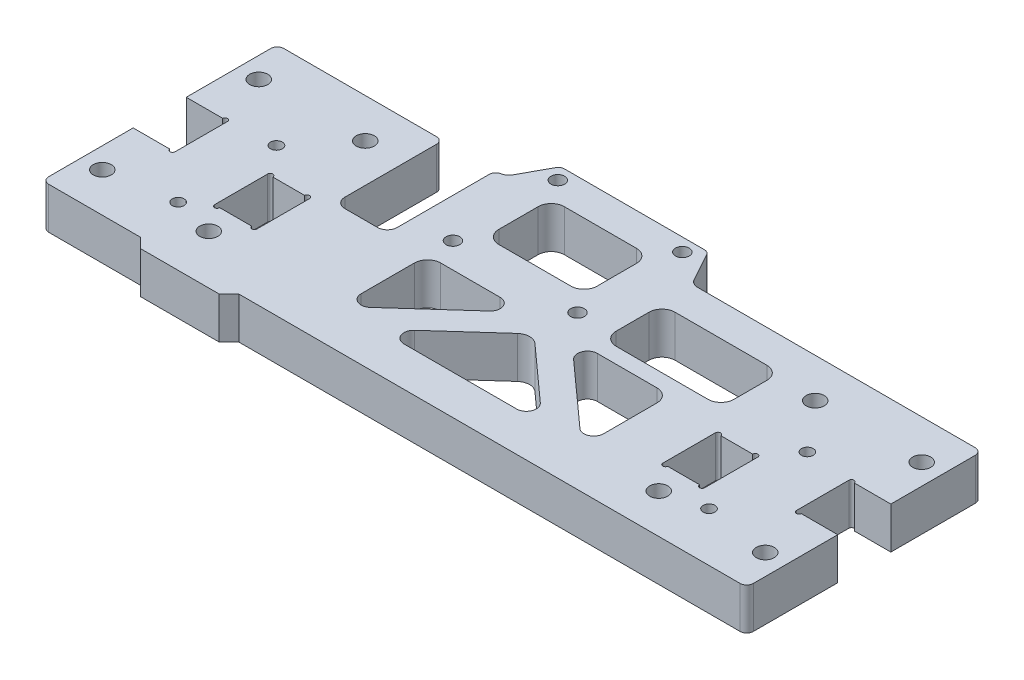
SolidWorks part; units mm, degrees
material "6061 Alloy"
ref_plane "Front Plane" through (0, 0, 0) normal (0, 0, 1) x (1, 0, 0)
ref_plane "Top Plane" through (0, 0, 0) normal (0, 1, 0) x (1, 0, 0)
ref_plane "Right Plane" through (0, 0, 0) normal (1, 0, 0) x (0, 0, -1)
sketch "Sketch1" plane through (0, 0, 0) normal (0, 1, 0) x (1, 0, 0)
  line L0 (107.5, 76.65) -> (107.5, 0) construction
  line L6 (32.7004, 36.1) -> (32.7004, 19.9)
  line L8 (45.6, 36) -> (45.6, 20)
  line L13 (0, 71.75) -> (69.5, 71.75)
  line L14 (69.5, 71.75) -> (75.5, 82.75)
  line L15 (75.5, 82.75) -> (120.5, 82.75)
  line L16 (120.5, 82.75) -> (126.5, 71.75)
  line L17 (126.5, 71.75) -> (215, 71.75)
  line L18 (32.7004, 28) -> (45.6, 28) construction
  line L19 (34.3004, 36.1) -> (44.0063, 36.1)
  line L20 (34.3004, 19.9) -> (44.0063, 19.9)
  line L21 (182.2996, 36.1) -> (182.2996, 19.9)
  line L22 (180.6996, 36.1) -> (170.9937, 36.1)
  line L23 (169.4, 36) -> (169.4, 20)
  line L24 (180.6996, 19.9) -> (170.9937, 19.9)
  line L25 (12.7, 35.875) -> (0, 35.875) construction
  line L29 (12.7, 43.975) -> (12.7, 27.775)
  line L30 (11.1189, 43.975) -> (0, 43.975)
  line L31 (11.1189, 27.775) -> (0, 27.775)
  line L32 (0, 27.775) -> (0, 0)
  line L33 (0, 43.975) -> (0, 71.75)
  line L34 (202.3, 35.875) -> (215, 35.875) construction
  line L35 (215, 43.975) -> (215, 71.75)
  line L36 (215, 27.775) -> (215, 0)
  line L37 (203.8811, 27.775) -> (215, 27.775)
  line L38 (203.8811, 43.975) -> (215, 43.975)
  line L39 (202.3, 43.975) -> (202.3, 27.775)
  line L40 (0, 0) -> (30, 0)
  line L41 (30, 0) -> (33, -3)
  line L42 (33, -3) -> (57, -3)
  line L43 (57, -3) -> (60, 0)
  line L44 (60, 0) -> (215, 0)
  circle A0 centre (38.85, 59.75) radius 2.75
  circle A5 centre (38.85, 12) radius 2.75
  circle A6 centre (176.15, 59.75) radius 2.75
  circle A7 centre (176.15, 12) radius 2.75
  arc A8 (32.7004, 36.1) -> (34.3004, 36.1) centre (33.5004, 36.1) cw
  arc A9 (45.6, 36) -> (44.0063, 36.1) centre (44.8, 36) ccw
  arc A10 (32.7004, 19.9) -> (34.3004, 19.9) centre (33.5004, 19.9) ccw
  arc A11 (45.6, 20) -> (44.0063, 19.9) centre (44.8, 20) cw
  arc A12 (182.2996, 19.9) -> (180.6996, 19.9) centre (181.4996, 19.9) cw
  arc A13 (182.2996, 36.1) -> (180.6996, 36.1) centre (181.4996, 36.1) ccw
  arc A14 (169.4, 36) -> (170.9937, 36.1) centre (170.2, 36) cw
  arc A15 (169.4, 20) -> (170.9937, 19.9) centre (170.2, 20) ccw
  circle A16 centre (6.35, 12) radius 2.75
  circle A17 centre (6.35, 59.75) radius 2.75
  arc A18 (12.7, 27.775) -> (11.1189, 27.775) centre (11.9095, 27.8976) cw
  arc A19 (12.7, 43.975) -> (11.1189, 43.975) centre (11.9095, 43.8524) ccw
  arc A20 (202.3, 43.975) -> (203.8811, 43.975) centre (203.0905, 43.8524) cw
  arc A21 (202.3, 27.775) -> (203.8811, 27.775) centre (203.0905, 27.8976) ccw
  circle A22 centre (208.65, 59.75) radius 2.75
  circle A23 centre (208.65, 12) radius 2.75
  dimension "D12" = 5.5
  dimension "D16" = 5.5
  dimension "D17" = 0.8
  dimension "D18" = 0.8
  dimension "D19" = 0.8
  dimension "D20" = 0.8
  dimension "D21" = 5.5
  dimension "D22" = 5.5
  dimension "D27" = 0.8
  dimension "D1" = 215
  dimension "D2" = 71.75
  dimension "D5" = 61.9
  dimension "D6" = 12.9
  dimension "D4" = 11
  dimension "D7" = 6
  dimension "D8" = 38
  dimension "D10" = 45
  dimension "D11" = 16.2
  dimension "D14" = 6
  dimension "D13" = 12
  dimension "D25" = 16.2
  dimension "D3" = 12
  dimension "D23" = 16.2
  dimension "D26" = 12.7
  dimension "D9" = 3
  dimension "D15" = 30
  dimension "D24" = 30
  dimension "D28" = 3
  dimension "D29" = 35.875
extrude "Boss-Extrude1" add sketch "Sketch1" along normal blind 12.7
sketch "Sketch2" plane through (0, 12.7, 0) normal (0, 1, 0) x (1, 0, 0)
  line L1 (50.6, 85.2461) -> (66.6, 85.2461)
  line L2 (50.6, 85.2461) -> (50.6, 38.75)
  line L3 (50.6, 38.75) -> (66.6, 38.75)
  line L4 (66.6, 85.2461) -> (66.6, 38.75)
  line L5 (45.6, 20) -> (45.6, 36) construction
  line L12 (69.5, 71.75) -> (0, 71.75) construction
  dimension "D1" = 5
  dimension "D2" = 16
  dimension "D3" = 33
extrude "Cut-Extrude1" cut sketch "Sketch2" against normal through all
sketch "Sketch3" plane through (0, 12.7, 0) normal (0, 1, 0) x (1, 0, 0)
  line L1 (66.6, 38.75) -> (66.6, 71.75) construction
  line L2 (120.5, 82.75) -> (75.5, 82.75) construction
  circle A0 centre (78.6, 78.75) radius 2.1
  circle A1 centre (78.6, 46.75) radius 2.1
  circle A2 centre (116.6, 78.75) radius 2.1
  circle A3 centre (116.6, 46.75) radius 2.1
  dimension "D2" = 4.2
  dimension "D5" = 4.2
  dimension "D8" = 32
  dimension "D1" = 4
  dimension "D3" = 12
  dimension "D4" = 32
  dimension "D7" = 38
  dimension "D6" = 2
extrude "Cut-Extrude2" cut sketch "Sketch3" against normal through all
sketch "Sketch5" plane through (0, 12.7, 0) normal (0, 1, 0) x (1, 0, 0)
  line L2 (83.6069, 16.5062) -> (102.789, 33.7701)
  line L3 (100.7821, 39) -> (82.6, 39)
  line L8 (78.6, 35) -> (78.6, 18.7361)
  line L12 (66.6, 38.75) -> (66.6, 71.75) construction
  line L13 (112.9241, 32.0917) -> (96.411, 17.2299)
  line L14 (115.6, 34.5) -> (115.6, 12) construction
  line L15 (98.4179, 12) -> (132.7821, 12)
  line L16 (118.2759, 32.0917) -> (134.789, 17.2299)
  line L17 (130.4179, 39) -> (148.6, 39)
  line L18 (147.5931, 16.5062) -> (128.411, 33.7701)
  line L19 (152.6, 35) -> (152.6, 18.7361)
  line L20 (120.5, 82.75) -> (75.5, 82.75) construction
  line L21 (86.6, 72.75) -> (108.6, 72.75)
  line L22 (82.6, 68.75) -> (82.6, 56.75)
  line L23 (86.6, 52.75) -> (108.6, 52.75)
  line L24 (112.6, 68.75) -> (112.6, 56.75)
  line L25 (215, 71.75) -> (126.5, 71.75) construction
  line L26 (131.4, 61.75) -> (159.4, 61.75)
  line L27 (127.4, 57.75) -> (127.4, 47.75)
  line L28 (131.4, 43.75) -> (159.4, 43.75)
  line L29 (163.4, 57.75) -> (163.4, 47.75)
  line L31 (169.4, 36) -> (169.4, 20) construction
  arc A0 (118.2759, 32.0917) -> (112.9241, 32.0917) centre (115.6, 29.1186) ccw
  arc A1 (152.6, 35) -> (148.6, 39) centre (148.6, 35) ccw
  arc A2 (78.6, 35) -> (82.6, 39) centre (82.6, 35) cw
  arc A3 (112.6, 68.75) -> (108.6, 72.75) centre (108.6, 68.75) ccw
  arc A4 (108.6, 52.75) -> (112.6, 56.75) centre (108.6, 56.75) ccw
  arc A5 (82.6, 56.75) -> (86.6, 52.75) centre (86.6, 56.75) ccw
  arc A6 (82.6, 68.75) -> (86.6, 72.75) centre (86.6, 68.75) cw
  arc A7 (147.5931, 16.5062) -> (152.6, 18.7361) centre (149.6, 18.7361) ccw
  arc A8 (128.411, 33.7701) -> (130.4179, 39) centre (130.4179, 36) cw
  arc A9 (83.6069, 16.5062) -> (78.6, 18.7361) centre (81.6, 18.7361) cw
  arc A10 (132.7821, 12) -> (134.789, 17.2299) centre (132.7821, 15) ccw
  arc A11 (98.4179, 12) -> (96.411, 17.2299) centre (98.4179, 15) cw
  arc A12 (102.789, 33.7701) -> (100.7821, 39) centre (100.7821, 36) ccw
  arc A13 (163.4, 57.75) -> (159.4, 61.75) centre (159.4, 57.75) ccw
  arc A14 (159.4, 43.75) -> (163.4, 47.75) centre (159.4, 47.75) ccw
  arc A15 (127.4, 47.75) -> (131.4, 43.75) centre (131.4, 47.75) ccw
  arc A16 (127.4, 57.75) -> (131.4, 61.75) centre (131.4, 57.75) cw
  point P25 (152.6, 39)
  point P28 (78.6, 39)
  point P33 (112.6, 52.75)
  point P36 (82.6, 52.75)
  point P39 (82.6, 72.75)
  point P42 (152.6, 12)
  point P45 (122.6, 39)
  point P48 (78.6, 12)
  point P51 (140.6, 12)
  point P54 (90.6, 12)
  point P57 (108.6, 39)
  point P68 (163.4, 61.75)
  point P71 (163.4, 43.75)
  point P76 (127.4, 61.75)
  dimension "D11" = 4
  dimension "D12" = 3
  dimension "D13" = 3
  dimension "D14" = 3
  dimension "D19" = 4
  dimension "D2" = 27
  dimension "D3" = 12
  dimension "D4" = 12
  dimension "D5" = 30
  dimension "D6" = 25
  dimension "D7" = 10
  dimension "D8" = 16
  dimension "D9" = 20
  dimension "D10" = 30
  dimension "D15" = 10
  dimension "D16" = 18
  dimension "D17" = 6
  dimension "D18" = 36
extrude "Cut-Extrude3" cut sketch "Sketch5" against normal through all
fillet "Fillet1" radius 3 4 edges at (69.5, 6.35, -71.75) (66.6, 6.35, -38.75) (50.6, 6.35, -38.75) (126.5, 6.35, -71.75)
fillet "Fillet2" radius 2 8 edges at (215, 6.35, -71.75) (120.5, 6.35, -82.75) (75.5, 6.35, -82.75) (50.6, 6.35, -71.75) (66.6, 6.35, -71.75) (0, 6.35, -71.75) (215, 6.35, 0) (0, 6.35, 0)
sketch "Sketch6" plane through (0, 12.7, 0) normal (0, 1, 0) x (1, 0, 0)
  line L0 (60, 0) -> (213, 0) construction
  line L1 (107.5, 92.584) -> (107.5, -38.973) construction
  line L2 (215, 2) -> (215, 27.775) construction
  circle A0 centre (188.5, 45) radius 1.8
  circle A1 centre (176.15, 59.75) radius 2.75 construction
  circle A2 centre (188.5, 15) radius 1.8
  circle A3 centre (26.5, 45) radius 1.8
  circle A4 centre (26.5, 15) radius 1.8
  dimension "D2" = 3.6
  dimension "D5" = 3.6
  dimension "D1" = 12.35
  dimension "D3" = 45
  dimension "D4" = 15
  dimension "D6" = 107.5
extrude "Cut-Extrude4" cut sketch "Sketch6" against normal through all
equation "\"DriveMotorLength\"= 90mm"
equation "\"DriveMotorGap\"= 10mm"
equation "\"AluminumThickness\"= 0.5in"
equation "\"ChassisWidth\"= ( \"DriveMotorLength\" + \"AluminumThickness\" ) * 2 + \"DriveMotorGap\""
equation "\"RepeatMagnumHoleWidth\"= 19.05mm"
equation "\"MortiseWidth\"= 16mm"
equation "\"ChassisScrewThruHole\"= 5.5mm"
equation "\"D11@Sketch1\"=\"MortiseSlotWidth\""
equation "\"D12@Sketch1\"=\"ChassisScrewThruHole\""
equation "\"D16@Sketch1\"=\"ChassisScrewThruHole\""
equation "\"MortiseSlotWidth\"= 16.2mm"
equation "\"Dogbone\"= 0.8mm"
equation "\"D17@Sketch1\"=\"Dogbone\""
equation "\"D18@Sketch1\"=\"Dogbone\""
equation "\"D19@Sketch1\"=\"Dogbone\""
equation "\"D20@Sketch1\"=\"Dogbone\""
equation "\"D21@Sketch1\"=\"ChassisScrewThruHole\""
equation "\"D22@Sketch1\"=\"ChassisScrewThruHole\""
equation "\"D27@Sketch1\"=\"Dogbone\""
equation "\"D23@Sketch1\"=\"MortiseSlotWidth\""
equation "\"D25@Sketch1\"=\"MortiseSlotWidth\""
